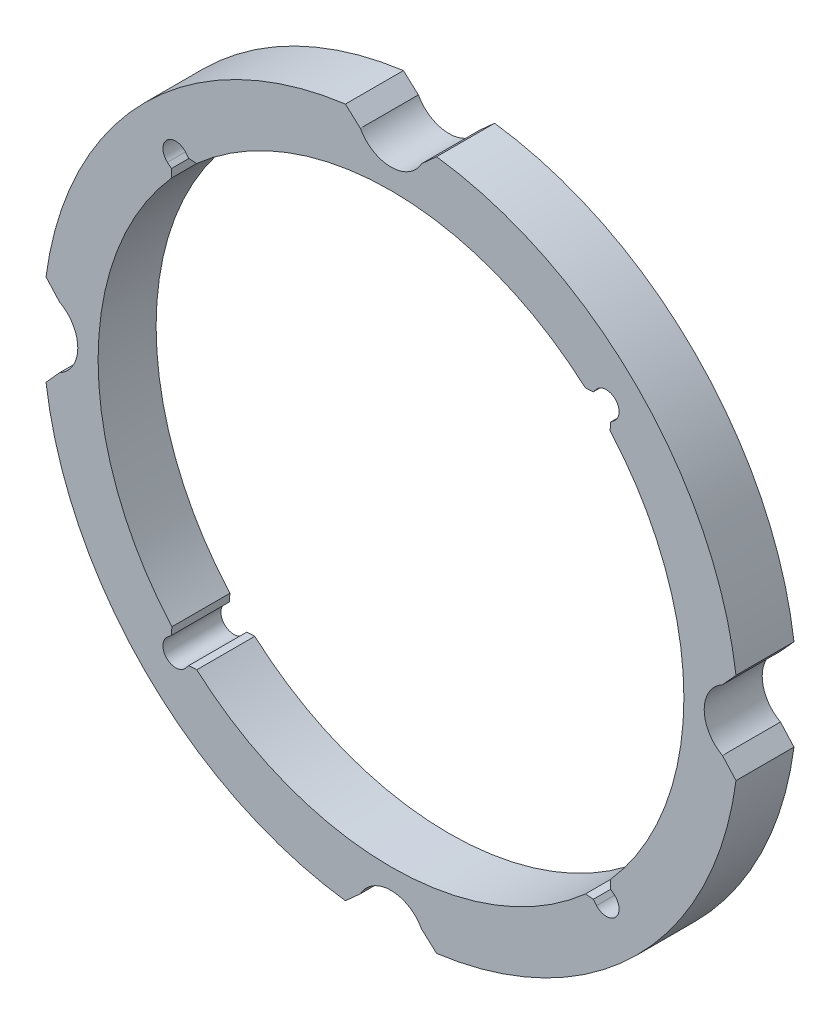
SolidWorks part; units mm, degrees
ref_plane "前视基准面" through (0, 0, 0) normal (0, 0, 1) x (1, 0, 0)
ref_plane "上视基准面" through (0, 0, 0) normal (0, 1, 0) x (1, 0, 0)
ref_plane "右视基准面" through (0, 0, 0) normal (1, 0, 0) x (0, 0, -1)
sketch "草图1" plane through (0, 0, 0) normal (0, 0, 1) x (1, 0, 0)
  line L0 (-38.5475, 35.4465) -> (-37.1231, 34.2363)
  line L1 (37.1231, -37.1231) -> (-37.1231, -37.1231) construction
  line L2 (37.1231, -37.1231) -> (37.1231, 37.1231) construction
  line L3 (37.1231, 37.1231) -> (-37.1231, 37.1231) construction
  line L4 (-37.1231, -37.1231) -> (-37.1231, 37.1231) construction
  line L5 (37.1231, -37.1231) -> (-37.1231, 37.1231) construction
  line L6 (37.1231, 37.1231) -> (-37.1231, -37.1231) construction
  line L7 (-35.4465, 38.5475) -> (-34.2363, 37.1231)
  line L8 (35.4465, 38.5475) -> (34.2363, 37.1231)
  line L9 (38.5475, 35.4465) -> (37.1231, 34.2363)
  line L10 (38.5475, -35.4465) -> (37.1231, -34.2363)
  line L11 (35.4465, -38.5475) -> (34.2363, -37.1231)
  line L12 (-35.4465, -38.5475) -> (-34.2363, -37.1231)
  line L13 (-38.5475, -35.4465) -> (-37.1231, -34.2363)
  arc A0 (-37.1231, 34.2363) -> (-37.1231, -34.2363) centre (0, 0) ccw
  arc A1 (-35.4465, 38.5475) -> (-38.5475, 35.4465) centre (-37.1231, 37.1231) ccw
  circle A5 centre (0, 0) radius 60
  arc A6 (38.5475, 35.4465) -> (35.4465, 38.5475) centre (37.1231, 37.1231) ccw
  arc A7 (35.4465, -38.5475) -> (38.5475, -35.4465) centre (37.1231, -37.1231) ccw
  arc A8 (-38.5475, -35.4465) -> (-35.4465, -38.5475) centre (-37.1231, -37.1231) ccw
  arc A9 (34.2363, 37.1231) -> (-34.2363, 37.1231) centre (0, 0) ccw
  arc A10 (-34.2363, -37.1231) -> (34.2363, -37.1231) centre (0, 0) ccw
  arc A11 (37.1231, -34.2363) -> (37.1231, 34.2363) centre (0, 0) ccw
  point P29 (0, 0)
  dimension "D1" = 101
  dimension "D3" = 4.4
  dimension "D4" = 4
  dimension "D7" = 120
  dimension "D2" = 105
extrude "凸台-拉伸1" add sketch "草图1" along normal blind 10
chamfer "倒角1" distance 1 angle 45 8 edges at (37.1231, -34.2363, 5) (34.2363, -37.1231, 5) (37.1231, 34.2363, 5) (34.2363, 37.1231, 5) (-34.2363, -37.1231, 5) (-37.1231, -34.2363, 5) (-34.2363, 37.1231, 5) (-37.1231, 34.2363, 5) first distance on face at (43.8116, 0, 5) first distance on face at (34.8414, -37.8353, 5) first distance on face at (37.8353, 34.8414, 5) first distance on face at (0, 43.8116, 5) first distance on face at (0, -43.8116, 5) first distance on face at (-37.8353, -34.8414, 5) first distance on face at (-34.8414, 37.8353, 5) first distance on face at (-43.8116, 0, 5)
sketch "草图2" plane through (0, 0, 0) normal (0, 0, -1) x (-1, 0, 0)
  circle A0 centre (60, 0) radius 6
  circle A1 centre (0, 0) radius 60 construction
  circle A2 centre (-60, 0) radius 6
  circle A3 centre (0, -60) radius 6
  circle A4 centre (0, 60) radius 6
  dimension "D1" = 12
  dimension "D2" = 12
  dimension "D3" = 12
  dimension "D4" = 12
extrude "切除-拉伸1" cut sketch "草图2" against normal blind 10
chamfer "倒角2" distance 2 angle 45 8 edges at (5.9925, 59.7, 5) (59.7, -5.9925, 5) (59.7, 5.9925, 5) (-5.9925, 59.7, 5) (5.9925, -59.7, 5) (-5.9925, -59.7, 5) (-59.7, -5.9925, 5) (-59.7, 5.9925, 5) first distance on face at (0, 56.85, 5) first distance on face at (56.85, 0, 5) first distance on face at (0, -56.85, 5) first distance on face at (-56.85, 0, 5)
